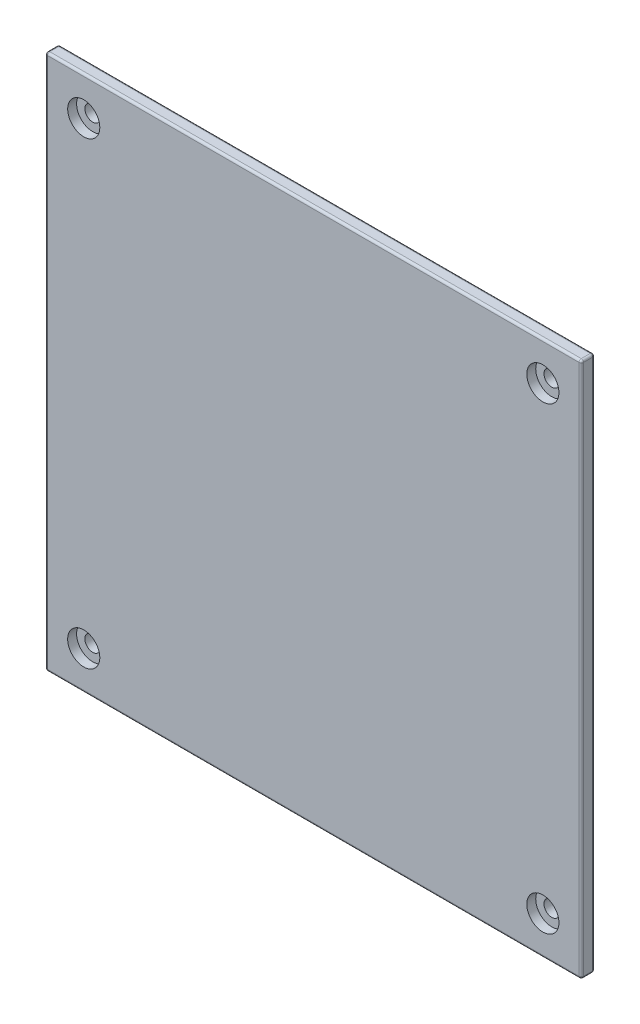
SolidWorks part; units mm, degrees
material "PVC 0.007 Plasticizado"
ref_plane "Plano frontal" through (0, 0, 0) normal (0, 0, 1) x (1, 0, 0)
ref_plane "Plano superior" through (0, 0, 0) normal (0, 1, 0) x (1, 0, 0)
ref_plane "Plano direito" through (0, 0, 0) normal (1, 0, 0) x (0, 0, -1)
sketch "Esboço1" plane through (0, 0, 0) normal (0, 0, 1) x (1, 0, 0)
  line L1 (-60, -60) -> (60, -60)
  line L2 (-60, -60) -> (-60, 60)
  line L3 (-60, 60) -> (60, 60)
  line L4 (60, -60) -> (60, 60)
  line L5 (-60, -60) -> (60, 60) construction
  line L6 (-60, 60) -> (60, -60) construction
  point P0 (0, 0)
  dimension "D1" = 120
  dimension "D2" = 120
extrude "Ressalto-extrusão1" add sketch "Esboço1" along normal blind 3
sketch "Esboço2" plane through (0, 0, 0) normal (0, 0, -1) x (-1, 0, 0)
  line L8 (-56.4, 56.4) -> (-56.4, -56.4)
  line L9 (-56.4, -56.4) -> (56.4, -56.4)
  line L10 (56.4, -56.4) -> (56.4, 56.4)
  line L11 (56.4, 56.4) -> (-56.4, 56.4)
  line L12 (-56.4, 56.4) -> (-56.4, -56.4)
  line L13 (-56.4, -56.4) -> (56.4, -56.4)
  line L14 (56.4, -56.4) -> (56.4, 56.4)
  line L15 (56.4, 56.4) -> (-56.4, 56.4)
  dimension "D1" = 3.6
extrude "Ressalto-extrusão2" add sketch "Esboço2" along normal blind 2
sketch "Esboço3" plane through (0, 0, -2) normal (0, 0, -1) x (-1, 0, 0)
  line L8 (54.4, 54.4) -> (-54.4, 54.4)
  line L9 (-54.4, 54.4) -> (-54.4, -54.4)
  line L10 (-54.4, -54.4) -> (54.4, -54.4)
  line L11 (54.4, -54.4) -> (54.4, 54.4)
  line L12 (54.4, 54.4) -> (-54.4, 54.4)
  line L13 (-54.4, 54.4) -> (-54.4, -54.4)
  line L14 (-54.4, -54.4) -> (54.4, -54.4)
  line L15 (54.4, -54.4) -> (54.4, 54.4)
  dimension "D1" = 2
extrude "Corte-extrusão1" cut sketch "Esboço3" against normal blind 2
sketch "Esboço5" plane through (0, 0, 0) normal (0, 0, -1) x (-1, 0, 0)
  line L0 (56.4, -56.4) -> (56.4, 56.4) construction
  line L1 (56.4, 56.4) -> (-56.4, 56.4) construction
  line L2 (60, 60) -> (60, -60) construction
  circle A0 centre (51.4, 51.4) radius 5
  dimension "D1" = 8.6
extrude "Ressalto-extrusão3" add sketch "Esboço5" along normal blind 2
mirror "Espelhar1" about plane through (0, 0, 0) normal (1, 0, 0) of "Ressalto-extrusão3"
mirror "Espelhar2" about plane through (0, 0, 0) normal (0, 1, 0) of "Espelhar1"
chamfer "Chanfro1" distance 0.5 angle 45 4 edges at (-56.4, 0, -2) (0, -56.4, -2) (56.4, 0, -2) (0, 56.4, -2)
fillet "Filete1" radius 2 8 edges at (0, -54.4, 0) (47.8645, -47.8645, 0) (54.4, 0, 0) (47.8645, 47.8645, 0) (0, 54.4, 0) (-47.8645, 47.8645, 0) (-54.4, 0, 0) (-47.8645, -47.8645, 0)
sketch "Esboço6" plane through (0, 0, 3) normal (0, 0, 1) x (1, 0, 0)
  line L0 (-60, 60) -> (-60, -60) construction
  line L1 (60, 60) -> (-60, 60) construction
  circle A0 centre (-51.4, 51.4) radius 3.6
  dimension "D1" = 8.6
  dimension "D3" = 7.2
  dimension "D2" = 8.6
extrude "Corte-extrusão2" cut sketch "Esboço6" against normal blind 2
sketch "Esboço7" plane through (0, 0, 1) normal (0, 0, 1) x (1, 0, 0)
  circle A0 centre (-51.4, 51.4) radius 1.75
  dimension "D1" = 3.5
extrude "Corte-extrusão3" cut sketch "Esboço7" against normal through all
mirror "Espelhar3" about plane through (0, 0, 0) normal (1, 0, 0) of "Corte-extrusão2", "Corte-extrusão3"
mirror "Espelhar4" about plane through (0, 0, 0) normal (0, 1, 0) of "Espelhar3"
fillet "Filete2" radius 0.5 12 edges at (0, -60, 3) (0, -60, 0) (60, -60, 1.5) (60, 0, 3) (60, 0, 0) (-60, 0, 3) (-60, -60, 1.5) (-60, 0, 0) (60, 60, 1.5) (0, 60, 3) (-60, 60, 1.5) (0, 60, 0)
ref_plane "MESA" through (0, 0, 3) normal (0, 0, 1) x (1, 0, 0)
